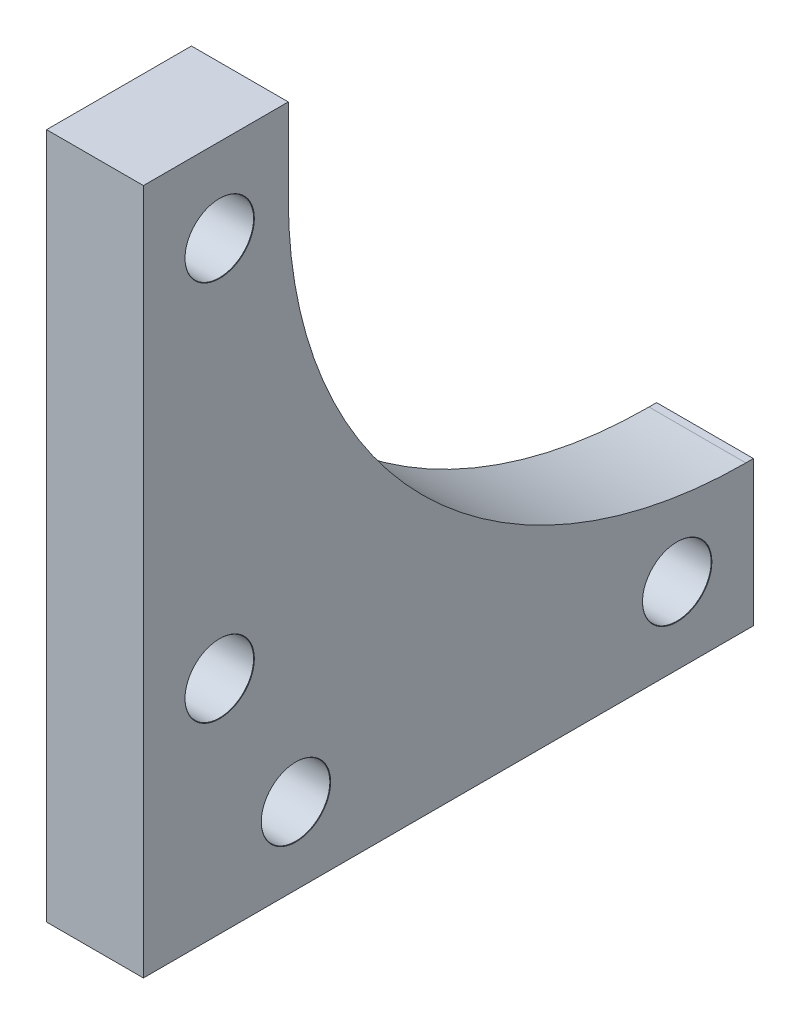
SolidWorks part; units mm, degrees
material "1060 Alloy"
ref_plane "Front Plane" through (0, 0, 0) normal (0, 0, 1) x (1, 0, 0)
ref_plane "Top Plane" through (0, 0, 0) normal (0, 1, 0) x (1, 0, 0)
ref_plane "Right Plane" through (0, 0, 0) normal (1, 0, 0) x (0, 0, -1)
sketch "Sketch1" plane through (0, 0, 0) normal (1, 0, 0) x (0, 0, -1)
  line L0 (0, 0) -> (0, 45)
  line L2 (40, 0) -> (0, 0)
  line L3 (0, 45) -> (9.5, 45)
  line L4 (9.5, 45) -> (9.5, 9.5)
  line L5 (9.5, 9.5) -> (40, 9.5)
  line L6 (40, 9.5) -> (40, 0)
  dimension "D1" = 40
  dimension "D2" = 9.5
  dimension "D3" = 45
extrude "Boss-Extrude1" add sketch "Sketch1" along normal blind 6.35
sketch "Sketch6" plane through (6.35, 0, 0) normal (1, 0, 0) x (0, 0, -1)
  line L0 (0, 45) -> (0, 0) construction
  line L1 (5, 39.5) -> (5, 14.5) construction
  line L2 (35, 5) -> (10, 5) construction
  line L3 (40, 9.5) -> (9.5, 9.5) construction
  line L5 (9.5, 9.5) -> (9.5, 45) construction
  point P11 (5, 39.5)
  point P12 (35, 5)
  point P13 (10, 5)
  dimension "D1" = 25
  dimension "D2" = 10
  dimension "D3" = 4.5
  dimension "D4" = 25
  dimension "D5" = 5
  dimension "D6" = 4.5
hole_wizard "M4 Clearance Hole1" positions "Sketch7" profile "Sketch9" hole size "M4" standard "ANSI Metric" end condition through all
sketch "Sketch7" plane through (6.35, 0, 0) normal (1, 0, 0) x (0, 0, -1)
  point P0 (35, 5)
  point P6 (10, 5)
  point P10 (5, 39.5)
  point P13 (5, 14.5)
sketch "Sketch9" plane through (6.35, 5, -35) normal (0, 1, 0) x (0, 0, -1)
  line L0 (0, 0) -> (0, 6.35)
  line L1 (0, 6.35) -> (2.25, 6.35)
  line L2 (2.25, 6.35) -> (2.25, 0.025)
  line L3 (2.25, 0.025) -> (2.275, 0)
  line L5 (2.275, 0) -> (0, 0)
  line L6 (-2.25, 0.025) -> (-2.275, 0) construction
  line L11 (0, -6.35) -> (0, 107.95) construction
  dimension "Thru Hole Dia." = 4.5
  dimension "Thru Hole Depth" = 6.35
  dimension "Near C'Sink Dia." = 4.55
  dimension "Near C'Sink Angle" = 90
fillet "Fillet1" radius 30 1 edges at (3.175, 9.5, -9.5)
